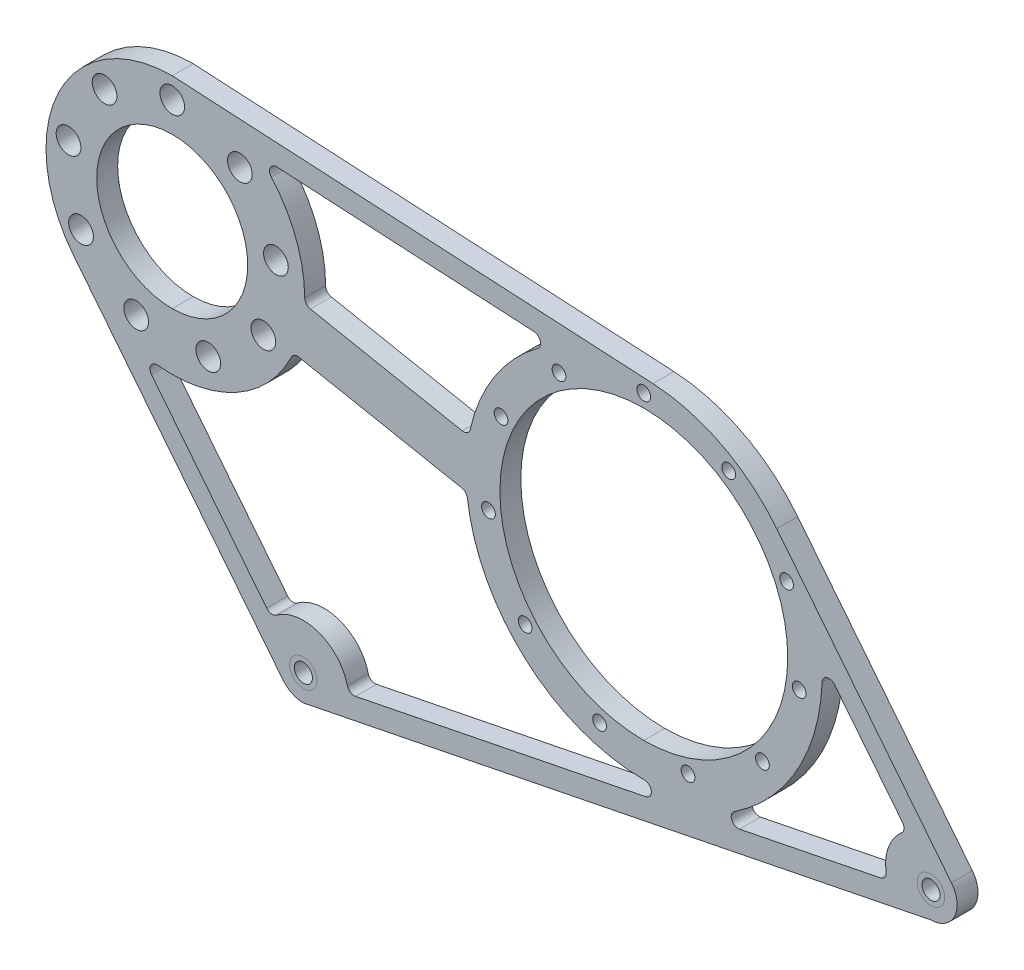
SolidWorks part; units mm, degrees
material "6061-T6 (SS)"
ref_plane "Front Plane" through (0, 0, 0) normal (0, 0, 1) x (1, 0, 0)
ref_plane "Top Plane" through (0, 0, 0) normal (0, 1, 0) x (1, 0, 0)
ref_plane "Right Plane" through (0, 0, 0) normal (1, 0, 0) x (0, 0, -1)
sketch "Sketch1" plane through (0, 0, 0) normal (0, 0, 1) x (1, 0, 0)
  line L0 (0, 0) -> (171.7726, -25.4) construction
  line L1 (47.761, -127.9853) -> (276.361, -82.1437)
  line L2 (0, 45.974) -> (175.1446, 36.4206)
  line L3 (-35.96, -28.6441) -> (40.3107, -124.3949)
  line L4 (220.1994, 13.1746) -> (283.8113, -66.6841)
  line L5 (171.7726, 36.5125) -> (171.7726, 27.0256) construction
  line L6 (0, 27.4955) -> (0, 45.974) construction
  circle A0 centre (0, 0) radius 45.974
  circle A1 centre (171.7726, -25.4) radius 61.9125
  circle A2 centre (171.7726, -25.4) radius 52.4256
  circle A3 centre (0, 0) radius 27.4955
  circle A4 centre (47.761, -118.4603) radius 9.525
  circle A5 centre (276.361, -72.6187) radius 9.525
  circle A6 centre (47.761, -118.4603) radius 3.2995
  circle A7 centre (276.361, -72.6187) radius 3.2995
  circle A19 centre (171.7726, -25.4) radius 57.1691 construction
  circle A21 centre (0, 0) radius 38.354 construction
  point P23 (0, 38.354)
  point P44 (0, 0)
  point P47 (171.7726, 31.7691)
  dimension "D1" = 91.948
  dimension "D2" = 123.825
  dimension "D5" = 104.8512
  dimension "D6" = 54.991
  dimension "D7" = 6.5989
  dimension "D8" = 6.5989
  dimension "D9" = 228.6
  dimension "D10" = 19.05
  dimension "D11" = 19.05
  dimension "D14" = 7.62
  dimension "D3" = 171.7726
  dimension "D4" = 25.4
  dimension "D12" = 117.2
  dimension "D13" = 76.2
extrude "Boss-Extrude1" add sketch "Sketch1" along normal blind 7.62 contours A5 L4 A1 L2 A0 L3 A4 L1 | L2 A0 A3 | A4 L1 A6 | A5 A7 | A1 A2 region at (43.7428, -126.7982, 0) region at (104.2025, -48.9688, 0) region at (268.0231, -68.6005, 0) region at (-40.2441, 19.3945, 0) region at (228.5635, -5.5459, 0)
sketch "Sketch2" plane through (0, 0, 7.62) normal (0, 0, 1) x (1, 0, 0)
  line L0 (171.7726, 36.5125) -> (171.7726, 27.0256) construction
  circle A0 centre (0, 38.354) radius 4.4996
  circle A1 centre (171.7726, 31.7691) radius 2.5006
  circle A2 centre (24.6535, 29.3809) radius 4.4996
  circle A3 centre (37.7713, 6.6601) radius 4.4996
  circle A4 centre (33.2155, -19.177) radius 4.4996
  circle A5 centre (13.1178, -36.041) radius 4.4996
  circle A6 centre (-13.1178, -36.041) radius 4.4996
  circle A7 centre (-33.2155, -19.177) radius 4.4996
  circle A8 centre (-37.7713, 6.6601) radius 4.4996
  circle A9 centre (-24.6535, 29.3809) radius 4.4996
  circle A10 centre (0, 0) radius 38.354 construction
  circle A11 centre (202.6805, 22.6937) radius 2.5006
  circle A12 centre (223.7754, -1.6511) radius 2.5006
  circle A13 centre (228.3597, -33.536) radius 2.5006
  circle A14 centre (214.9781, -62.8378) radius 2.5006
  circle A15 centre (187.879, -80.2533) radius 2.5006
  circle A16 centre (155.6662, -80.2533) radius 2.5006
  circle A17 centre (128.5671, -62.8378) radius 2.5006
  circle A18 centre (115.1854, -33.536) radius 2.5006
  circle A19 centre (119.7698, -1.6511) radius 2.5006
  circle A20 centre (140.8647, 22.6937) radius 2.5006
  circle A21 centre (171.7726, -25.4) radius 57.169 construction
  point P26 (0, 0)
  point P48 (171.7726, -25.4)
  dimension "D1" = 8.9992
  dimension "D2" = 5.0013
  dimension "D3" = 9
extrude "Cut-Extrude1" cut sketch "Sketch2" against normal through all both and the other way through all
ref_plane "Plane1" through (2.54, 0, 0) normal (1, 0, 0) x (0, 0, -1)
ref_plane "Plane2" through (171.7726, 0, 0) normal (1, 0, 0) x (0, 0, -1)
split line "Split Line5"
sketch "Sketch1<4>" plane through (0, 0, 0) normal (0, 0, 1) x (1, 0, 0) same geometry as "Sketch1"
sketch "Sketch4" plane through (0, 0, 7.62) normal (0, 0, 1) x (1, 0, 0)
  circle A0 centre (276.361, -72.6187) radius 3.2995
  circle A1 centre (276.361, -72.6187) radius 5
  circle A2 centre (47.761, -118.4603) radius 3.2995
  circle A3 centre (47.761, -118.4603) radius 5
  dimension "D1" = 10
  dimension "D2" = 6.5989
split line "Split Line6"
split line "Split Line7"
split line "Split Line8"
sketch "Sketch5" plane through (0, 0, 0) normal (0, 0, -1) x (-1, 0, 0)
  line L1 (-265.9885, -56.5395) -> (-241.2452, -25.4765)
  line L2 (-258.0382, -78.0463) -> (-206.6499, -88.3513)
  line L3 (-131.755, 31.156) -> (-38.1271, 36.263)
  line L4 (-105.593, -13.2277) -> (-50.3134, -2.4384)
  line L5 (-172.497, -95.2) -> (-66.7598, -116.4038)
  line L6 (-34.4084, -104.755) -> (7.5527, -52.0767)
  line L7 (-105.4771, -31.3206) -> (-46.1613, -19.7435)
  line L8 (0, 45.974) -> (-175.1446, 36.4206) construction
  line L9 (35.96, -28.6441) -> (-40.3107, -124.3949) construction
  line L10 (-47.761, -127.9853) -> (-276.361, -82.1437) construction
  line L11 (-220.1994, 13.1746) -> (-283.8113, -66.6841) construction
  line L12 (-171.7726, -25.4) -> (-171.7726, 974.6) construction
  arc A0 (-265.6497, -60.0549) -> (-260.0484, -75.1642) centre (-276.361, -72.6187) cw
  arc A1 (-36.0893, 32.0404) -> (-48.26, 0.0519) centre (0, 0) ccw
  arc A2 (-133.1319, 26.5813) -> (-108.5586, -11.2882) centre (-171.7726, -25.4) cw
  arc A3 (-63.7938, -114.5196) -> (-37.9106, -105.2108) centre (-47.761, -118.4603) cw
  arc A4 (-171.9891, -90.1696) -> (-107.5106, -33.496) centre (-171.7726, -25.4) ccw
  arc A5 (5.2877, -47.9695) -> (-43.391, -21.1246) centre (0, 0) cw
  arc A6 (-236.7202, -26.9651) -> (-204.7539, -83.7393) centre (-165.6488, -24.3352) ccw
  arc A7 (-265.6497, -60.0549) -> (-265.9885, -56.5395) centre (-264.0018, -58.122) cw
  arc A8 (-260.0484, -75.1642) -> (-258.0382, -78.0463) centre (-257.5388, -75.5559) ccw
  arc A9 (-206.6499, -88.3513) -> (-204.7539, -83.7393) centre (-206.1505, -85.8609) ccw
  arc A10 (-241.2452, -25.4765) -> (-236.7202, -26.9651) centre (-239.2584, -27.0591) cw
  arc A11 (-37.9106, -105.2108) -> (-34.4084, -104.755) centre (-36.3952, -103.1724) ccw
  arc A12 (-66.7598, -116.4038) -> (-63.7938, -114.5196) centre (-66.2604, -113.9133) ccw
  arc A13 (-172.497, -95.2) -> (-171.9891, -90.1696) centre (-171.9976, -92.7096) cw
  arc A14 (7.5527, -52.0767) -> (5.2877, -47.9695) centre (5.566, -50.4942) ccw
  arc A15 (-43.391, -21.1246) -> (-46.1613, -19.7435) centre (-45.6747, -22.2364) ccw
  arc A16 (-107.5106, -33.496) -> (-105.4771, -31.3206) centre (-104.9905, -33.8135) cw
  arc A17 (-108.5586, -11.2882) -> (-105.593, -13.2277) centre (-106.0796, -10.7347) ccw
  arc A18 (-48.26, 0.0519) -> (-50.3134, -2.4384) centre (-50.8, 0.0546) cw
  arc A19 (-38.1271, 36.263) -> (-36.0893, 32.0404) centre (-37.9887, 33.7268) cw
  arc A20 (-131.755, 31.156) -> (-133.1319, 26.5813) centre (-131.6166, 28.6198) ccw
  point P1 (-186.9027, -95.8114)
  point P11 (-51.881, -23.6816)
  point P20 (-36.0531, 36.376)
  point P23 (-186.9027, -95.8114)
  point P24 (0, 0)
  point P25 (-170.4092, -27.7502)
  point P26 (-186.9027, -94.2023)
  point P37 (-152.2296, -99.2643)
  point P38 (-156.4764, -98.4127)
  point P39 (0, 0)
  point P41 (-267.6332, -58.6042)
  point P44 (-260.5992, -77.5327)
  point P47 (-185.8867, -92.515)
  point P50 (-236.6152, -19.6641)
  point P51 (5.2086, -55.0195)
  point P52 (-148.0418, -15.6092)
  point P53 (-124.7696, 31.537)
  point P54 (-171.7726, -29.8582)
  point P57 (-171.7726, -35.6112)
  point P59 (0, 0)
  point P60 (4.353, -56.5395)
  point P61 (-103.6167, -12.7)
  point P62 (-102.8893, -12.7)
  point P63 (0, 0)
  point P65 (-131.5071, 31.7691)
  point P66 (-103.2189, -22.9834)
  point P67 (0, 0)
  point P68 (0, 0)
  point P80 (-44.2058, -19.3618)
  point P83 (-107.3075, -31.6778)
  dimension "D1" = 16.51
  dimension "D6" = 71.12
  dimension "D7" = 2.54
  dimension "D8" = 16.51
  dimension "D11" = 64.77
  dimension "D13" = 64.77
  dimension "D14" = 48.26
  dimension "D15" = 2.54
  dimension "D16" = 48.26
  dimension "D17" = 17.78
  dimension "D2" = 49.784
  dimension "D3" = 76.2
  dimension "D4" = 7.62
  dimension "D5" = 7.62
  dimension "D9" = 7.62
  dimension "D10" = 7.62
  dimension "D12" = 7.62
extrude "Cut-Extrude2" cut sketch "Sketch5" against normal through all both and the other way through all
